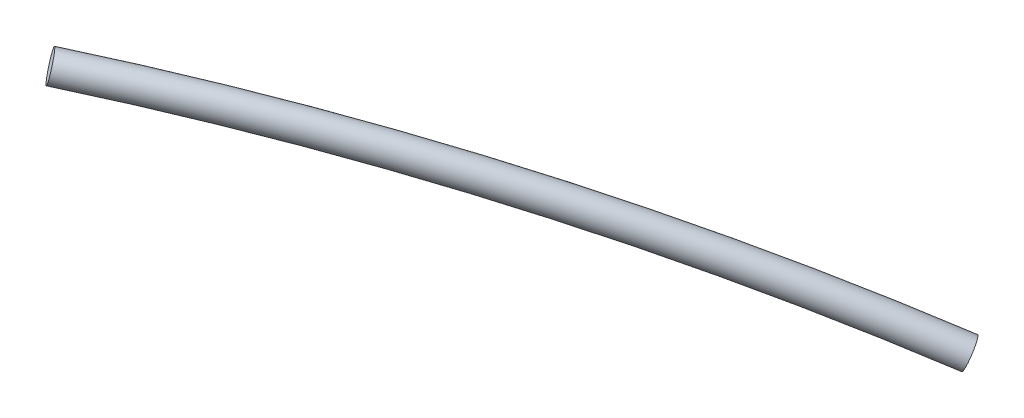
SolidWorks part; units mm, degrees
ref_plane "Front" through (0, 0, 0) normal (0, 0, 1) x (1, 0, 0)
ref_plane "Top" through (0, 0, 0) normal (0, 1, 0) x (1, 0, 0)
ref_plane "Right" through (0, 0, 0) normal (1, 0, 0) x (0, 0, -1)
ref_plane "Plane1" through (-4086.3835, -2369.8584, -3771.7716) normal (0.676, 0.392, 0.624) x (0.5398, 0.313, -0.7815)
sketch "Sketch1" plane through (-4086.3835, -2369.8584, -3771.7716) normal (0.676, 0.392, 0.624) x (0.5398, 0.313, -0.7815)
  line L0 (15737.4142, 886.5292) -> (13843.1881, 2415.5221) construction
  line L1 (13843.1881, 2415.5221) -> (12229.9309, 3469.8976) construction
  line L2 (15737.4142, 886.5292) -> (15958.1287, 668.4753) construction
  line L3 (14790.3011, 1651.0256) -> (14828.6448, 1698.5285) construction
  arc A0 (13843.1881, 2415.5221) -> (15737.4142, 886.5292) centre (7188.2057, -7766.9958) cw
  dimension "D1" = 2438.4
  dimension "D2" = 2743.2
  dimension "D3" = 61.0472
sketch "Sketch2" plane through (7456.2008, -2168.5766, -6715.5913) normal (0.7263, -0.2112, -0.6541) x (-0.6281, 0.1827, -0.7564)
  circle A0 centre (10410.2679, 4498.7913) radius 50.8
  circle A1 centre (10410.2679, 4498.7913) radius 50.8 construction
sweep "Sweep1" add profiles "Sketch2" path "Sketch1"
ref_axis "Axis1" through (3963.2384, 3323.2673, -25553.0538) along (0, 0, 1)
